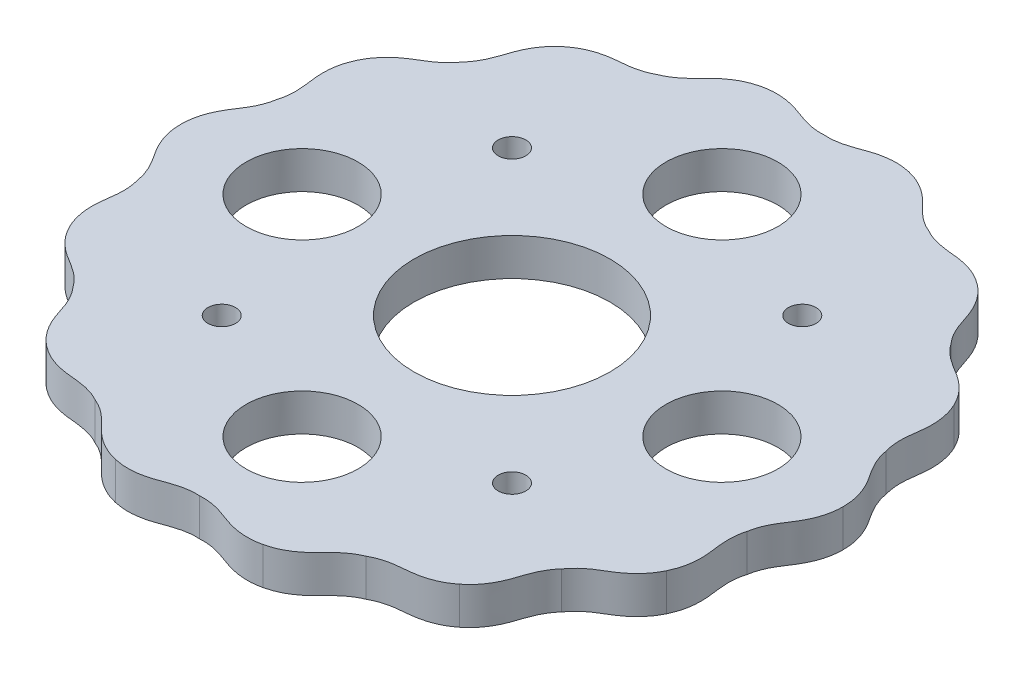
SolidWorks part; units mm, degrees
ref_plane "Front Plane" through (0, 0, 0) normal (0, 0, 1) x (1, 0, 0)
ref_plane "Top Plane" through (0, 0, 0) normal (0, 1, 0) x (1, 0, 0)
ref_plane "Right Plane" through (0, 0, 0) normal (1, 0, 0) x (0, 0, -1)
sketch "Sketch1" plane through (0, 0, 0) normal (0, 1, 0) x (1, 0, 0)
  line L0 (0, 0) -> (37.5, 0) construction
  line L1 (0, 0) -> (37.4807, 1.2019) construction
  line L2 (0, 0) -> (37.423, 2.4026) construction
  line L3 (0, 0) -> (37.3267, 3.6009) construction
  line L4 (0, 0) -> (37.1921, 4.7954) construction
  line L5 (0, 0) -> (37.0193, 5.985) construction
  line L6 (0, 0) -> (36.8085, 7.1684) construction
  line L7 (0, 0) -> (36.5598, 8.3445) construction
  line L8 (0, 0) -> (36.2736, 9.512) construction
  line L9 (0, 0) -> (35.95, 10.6698) construction
  line L10 (0, 0) -> (35.5896, 11.8166) construction
  line L11 (0, 0) -> (35.1926, 12.9512) construction
  line L12 (0, 0) -> (34.7594, 14.0725) construction
  line L13 (0, 0) -> (34.2905, 15.1794) construction
  line L14 (0, 0) -> (33.7863, 16.2706) construction
  line L15 (37.5, 0) -> (38.5, 0) construction
  line L16 (37.4807, 1.2019) -> (38.3521, 1.6927) construction
  line L17 (37.423, 2.4026) -> (37.9413, 3.2578) construction
  line L18 (37.3267, 3.6009) -> (37.3588, 4.6003) construction
  line L19 (37.1921, 4.7954) -> (36.7296, 5.682) construction
  line L20 (37.0193, 5.985) -> (36.1812, 6.5305) construction
  line L21 (36.8085, 7.1684) -> (35.8105, 7.2325) construction
  line L22 (36.5598, 8.3445) -> (35.5849, 8.122) construction
  line L23 (37, 0.0019) -> (37, 0)
  line L24 (33.3367, 16.052) -> (33.3358, 16.0537)
  line L25 (37, -0.0019) -> (37, 0)
  line L26 (33.3367, -16.052) -> (33.3358, -16.0537)
  line L27 (33.335, -16.0554) -> (33.3358, -16.0537)
  line L28 (23.0706, -28.9266) -> (23.0691, -28.9278)
  line L29 (23.0677, -28.9289) -> (23.0691, -28.9278)
  line L30 (8.2351, -36.0719) -> (8.2333, -36.0723)
  line L31 (8.2315, -36.0727) -> (8.2333, -36.0723)
  line L32 (-8.2315, -36.0727) -> (-8.2333, -36.0723)
  line L33 (-8.2351, -36.0719) -> (-8.2333, -36.0723)
  line L34 (-23.0677, -28.9289) -> (-23.0691, -28.9278)
  line L35 (-23.0706, -28.9266) -> (-23.0691, -28.9278)
  line L36 (-33.335, -16.0554) -> (-33.3358, -16.0537)
  line L37 (-33.3367, -16.052) -> (-33.3358, -16.0537)
  line L38 (-37, -0.0019) -> (-37, 0)
  line L39 (-37, 0.0019) -> (-37, 0)
  line L40 (-33.3367, 16.052) -> (-33.3358, 16.0537)
  line L41 (-33.335, 16.0554) -> (-33.3358, 16.0537)
  line L42 (-23.0706, 28.9266) -> (-23.0691, 28.9278)
  line L43 (-23.0677, 28.9289) -> (-23.0691, 28.9278)
  line L44 (-8.2351, 36.0719) -> (-8.2333, 36.0723)
  line L45 (-8.2315, 36.0727) -> (-8.2333, 36.0723)
  line L46 (8.2315, 36.0727) -> (8.2333, 36.0723)
  line L47 (8.2351, 36.0719) -> (8.2333, 36.0723)
  line L48 (23.0677, 28.9289) -> (23.0691, 28.9278)
  line L49 (23.0706, 28.9266) -> (23.0691, 28.9278)
  line L50 (33.335, 16.0554) -> (33.3358, 16.0537)
  line L51 (35.5, 0.0037) -> (35.5, 0)
  line L52 (31.986, 15.3995) -> (31.9844, 15.4029)
  line L53 (35.5, -0.0037) -> (35.5, 0)
  line L54 (31.986, -15.3995) -> (31.9844, -15.4029)
  line L55 (31.9828, -15.4062) -> (31.9844, -15.4029)
  line L56 (22.1368, -27.7527) -> (22.1339, -27.755)
  line L57 (22.131, -27.7573) -> (22.1339, -27.755)
  line L58 (7.9031, -34.6091) -> (7.8995, -34.6099)
  line L59 (7.8959, -34.6108) -> (7.8995, -34.6099)
  line L60 (-7.8959, -34.6108) -> (-7.8995, -34.6099)
  line L61 (-7.9031, -34.6091) -> (-7.8995, -34.6099)
  line L62 (-22.131, -27.7573) -> (-22.1339, -27.755)
  line L63 (-22.1368, -27.7527) -> (-22.1339, -27.755)
  line L64 (-31.9828, -15.4062) -> (-31.9844, -15.4029)
  line L65 (-31.986, -15.3995) -> (-31.9844, -15.4029)
  line L66 (-35.5, -0.0037) -> (-35.5, 0)
  line L67 (-35.5, 0.0037) -> (-35.5, 0)
  line L68 (-31.986, 15.3995) -> (-31.9844, 15.4029)
  line L69 (-31.9828, 15.4062) -> (-31.9844, 15.4029)
  line L70 (-22.1368, 27.7527) -> (-22.1339, 27.755)
  line L71 (-22.131, 27.7573) -> (-22.1339, 27.755)
  line L72 (-7.9031, 34.6091) -> (-7.8995, 34.6099)
  line L73 (-7.8959, 34.6108) -> (-7.8995, 34.6099)
  line L74 (7.8959, 34.6108) -> (7.8995, 34.6099)
  line L75 (7.9031, 34.6091) -> (7.8995, 34.6099)
  line L76 (22.131, 27.7573) -> (22.1339, 27.755)
  line L77 (22.1368, 27.7527) -> (22.1339, 27.755)
  line L78 (31.9828, 15.4062) -> (31.9844, 15.4029)
  circle A0 centre (0, 0) radius 35 construction
  circle A1 centre (37.5, 0) radius 2.5 construction
  circle A2 centre (0, 0) radius 37.5 construction
  spline S0 degree 3 poles (35.5849, 8.122) (35.6266, 7.5364) (36.0345, 6.7125) (36.7836, 5.6218) (37.4152, 4.5501) (38.2239, 2.702) (38.5014, 1.1074) (38.5, 0) knots 0 0 0 0 0.195516 0.310928 0.453873 0.621058 1 1 1 1
  spline S1 degree 3 poles (35.5849, 8.122) (35.3683, 8.6678) (35.3784, 9.5871) (35.5801, 10.8948) (35.6841, 12.1344) (35.611, 14.1503) (35.169, 15.7074) (34.6873, 16.7045) knots 0 0 0 0 0.195516 0.310928 0.453873 0.621058 1 1 1 1
  spline S2 degree 1 poles (34.1119, 7.7858) (33.3367, 16.052) knots 0 0 1 1 construction
  spline S3 degree 1 poles (34.1119, 7.7858) (37, 0.0019) knots 0 0 1 1 construction
  spline S4 degree 3 poles (33.3367, 16.052) (33.6005, 15.5058) (33.9037, 14.6401) (34.1146, 13.4372) (34.174, 12.5211) (34.1413, 11.5771) (34.0239, 10.6392) (33.8823, 9.6155) (33.9055, 8.625) (34.0243, 8.0514) (34.1119, 7.7858) knots 0.015853 0.015853 0.015853 0.015853 0.26189 0.384908 0.507927 0.630945 0.753963 0.876982 0.938491 1 1 1 1
  spline S5 degree 3 poles (34.1119, 7.7858) (34.1483, 7.5085) (34.2901, 6.9402) (34.6989, 6.0377) (35.2706, 5.1769) (35.7834, 4.3828) (36.2224, 3.5464) (36.5664, 2.6953) (36.8983, 1.52) (37.0008, 0.6085) (37, 0.0019) knots 0.015853 0.015853 0.015853 0.015853 0.077362 0.138872 0.26189 0.384908 0.507927 0.630945 0.753963 1 1 1 1
  spline S6 degree 3 poles (37, -0.0019) (37.0008, -0.6085) (36.8983, -1.52) (36.5664, -2.6953) (36.2224, -3.5464) (35.7834, -4.3828) (35.2706, -5.1769) (34.6989, -6.0377) (34.2901, -6.9402) (34.1483, -7.5085) (34.1119, -7.7858) knots 0.015853 0.015853 0.015853 0.015853 0.26189 0.384908 0.507927 0.630945 0.753963 0.876982 0.938491 1 1 1 1
  spline S7 degree 3 poles (34.1119, -7.7858) (34.0243, -8.0514) (33.9055, -8.625) (33.8823, -9.6155) (34.0239, -10.6392) (34.1413, -11.5771) (34.174, -12.5211) (34.1146, -13.4372) (33.9037, -14.6401) (33.6005, -15.5058) (33.3367, -16.052) knots 0.015853 0.015853 0.015853 0.015853 0.077362 0.138872 0.26189 0.384908 0.507927 0.630945 0.753963 1 1 1 1
  spline S8 degree 3 poles (33.335, -16.0554) (33.0725, -16.6022) (32.5847, -17.3791) (31.7758, -18.2939) (31.0965, -18.9115) (30.3381, -19.4746) (29.5316, -19.9675) (28.6429, -20.4951) (27.8831, -21.1308) (27.5087, -21.5813) (27.3556, -21.8154) knots 0.015853 0.015853 0.015853 0.015853 0.26189 0.384908 0.507927 0.630945 0.753963 0.876982 0.938491 1 1 1 1
  spline S9 degree 3 poles (27.3556, -21.8154) (27.1615, -22.0167) (26.8056, -22.4819) (26.3549, -23.3642) (26.0383, -24.348) (25.7371, -25.2439) (25.357, -26.1087) (24.906, -26.9083) (24.1941, -27.9005) (23.5453, -28.549) (23.0706, -28.9266) knots 0.015853 0.015853 0.015853 0.015853 0.077362 0.138872 0.26189 0.384908 0.507927 0.630945 0.753963 1 1 1 1
  spline S10 degree 3 poles (23.0677, -28.9289) (22.5939, -29.3077) (21.8173, -29.796) (20.6915, -30.2693) (19.8116, -30.531) (18.884, -30.7092) (17.9435, -30.8034) (16.9139, -30.8931) (15.9535, -31.1362) (15.4207, -31.3797) (15.1812, -31.5241) knots 0.015853 0.015853 0.015853 0.015853 0.26189 0.384908 0.507927 0.630945 0.753963 0.876982 0.938491 1 1 1 1
  spline S11 degree 3 poles (15.1812, -31.5241) (14.919, -31.6213) (14.3964, -31.886) (13.6076, -32.4854) (12.8955, -33.2344) (12.2354, -33.9109) (11.5177, -34.5251) (10.7645, -35.0499) (9.6926, -35.6349) (8.8266, -35.9377) (8.2351, -36.0719) knots 0.015853 0.015853 0.015853 0.015853 0.077362 0.138872 0.26189 0.384908 0.507927 0.630945 0.753963 1 1 1 1
  spline S12 degree 3 poles (8.2315, -36.0727) (7.6402, -36.2085) (6.7287, -36.3114) (5.5091, -36.2494) (4.6028, -36.1034) (3.6897, -35.8614) (2.8014, -35.5383) (1.8349, -35.1724) (0.8641, -34.9747) (0.2785, -34.9629) (0, -34.9891) knots 0.015853 0.015853 0.015853 0.015853 0.26189 0.384908 0.507927 0.630945 0.753963 0.876982 0.938491 1 1 1 1
  spline S13 degree 3 poles (0, -34.9891) (-0.2785, -34.9629) (-0.8641, -34.9747) (-1.8349, -35.1724) (-2.8014, -35.5383) (-3.6897, -35.8614) (-4.6028, -36.1034) (-5.5091, -36.2494) (-6.7287, -36.3114) (-7.6402, -36.2085) (-8.2315, -36.0727) knots 0.015853 0.015853 0.015853 0.015853 0.077362 0.138872 0.26189 0.384908 0.507927 0.630945 0.753963 1 1 1 1
  spline S14 degree 3 poles (-8.2351, -36.0719) (-8.8266, -35.9377) (-9.6926, -35.6349) (-10.7645, -35.0499) (-11.5177, -34.5251) (-12.2354, -33.9109) (-12.8955, -33.2344) (-13.6076, -32.4854) (-14.3964, -31.886) (-14.919, -31.6213) (-15.1812, -31.5241) knots 0.015853 0.015853 0.015853 0.015853 0.26189 0.384908 0.507927 0.630945 0.753963 0.876982 0.938491 1 1 1 1
  spline S15 degree 3 poles (-15.1812, -31.5241) (-15.4207, -31.3797) (-15.9535, -31.1362) (-16.9139, -30.8931) (-17.9435, -30.8034) (-18.884, -30.7092) (-19.8116, -30.531) (-20.6915, -30.2693) (-21.8173, -29.796) (-22.5939, -29.3077) (-23.0677, -28.9289) knots 0.015853 0.015853 0.015853 0.015853 0.077362 0.138872 0.26189 0.384908 0.507927 0.630945 0.753963 1 1 1 1
  spline S16 degree 3 poles (-23.0706, -28.9266) (-23.5453, -28.549) (-24.1941, -27.9005) (-24.906, -26.9083) (-25.357, -26.1087) (-25.7371, -25.2439) (-26.0383, -24.348) (-26.3549, -23.3642) (-26.8056, -22.4819) (-27.1615, -22.0167) (-27.3556, -21.8154) knots 0.015853 0.015853 0.015853 0.015853 0.26189 0.384908 0.507927 0.630945 0.753963 0.876982 0.938491 1 1 1 1
  spline S17 degree 3 poles (-27.3556, -21.8154) (-27.5087, -21.5813) (-27.8831, -21.1308) (-28.6429, -20.4951) (-29.5316, -19.9675) (-30.3381, -19.4746) (-31.0965, -18.9115) (-31.7758, -18.2939) (-32.5847, -17.3791) (-33.0725, -16.6022) (-33.335, -16.0554) knots 0.015853 0.015853 0.015853 0.015853 0.077362 0.138872 0.26189 0.384908 0.507927 0.630945 0.753963 1 1 1 1
  spline S18 degree 3 poles (-33.3367, -16.052) (-33.6005, -15.5058) (-33.9037, -14.6401) (-34.1146, -13.4372) (-34.174, -12.5211) (-34.1413, -11.5771) (-34.0239, -10.6392) (-33.8823, -9.6155) (-33.9055, -8.625) (-34.0243, -8.0514) (-34.1119, -7.7858) knots 0.015853 0.015853 0.015853 0.015853 0.26189 0.384908 0.507927 0.630945 0.753963 0.876982 0.938491 1 1 1 1
  spline S19 degree 3 poles (-34.1119, -7.7858) (-34.1483, -7.5085) (-34.2901, -6.9402) (-34.6989, -6.0377) (-35.2706, -5.1769) (-35.7834, -4.3828) (-36.2224, -3.5464) (-36.5664, -2.6953) (-36.8983, -1.52) (-37.0008, -0.6085) (-37, -0.0019) knots 0.015853 0.015853 0.015853 0.015853 0.077362 0.138872 0.26189 0.384908 0.507927 0.630945 0.753963 1 1 1 1
  spline S20 degree 3 poles (-37, 0.0019) (-37.0008, 0.6085) (-36.8983, 1.52) (-36.5664, 2.6953) (-36.2224, 3.5464) (-35.7834, 4.3828) (-35.2706, 5.1769) (-34.6989, 6.0377) (-34.2901, 6.9402) (-34.1483, 7.5085) (-34.1119, 7.7858) knots 0.015853 0.015853 0.015853 0.015853 0.26189 0.384908 0.507927 0.630945 0.753963 0.876982 0.938491 1 1 1 1
  spline S21 degree 3 poles (-34.1119, 7.7858) (-34.0243, 8.0514) (-33.9055, 8.625) (-33.8823, 9.6155) (-34.0239, 10.6392) (-34.1413, 11.5771) (-34.174, 12.5211) (-34.1146, 13.4372) (-33.9037, 14.6401) (-33.6005, 15.5058) (-33.3367, 16.052) knots 0.015853 0.015853 0.015853 0.015853 0.077362 0.138872 0.26189 0.384908 0.507927 0.630945 0.753963 1 1 1 1
  spline S22 degree 3 poles (-33.335, 16.0554) (-33.0725, 16.6022) (-32.5847, 17.3791) (-31.7758, 18.2939) (-31.0965, 18.9115) (-30.3381, 19.4746) (-29.5316, 19.9675) (-28.6429, 20.4951) (-27.8831, 21.1308) (-27.5087, 21.5813) (-27.3556, 21.8154) knots 0.015853 0.015853 0.015853 0.015853 0.26189 0.384908 0.507927 0.630945 0.753963 0.876982 0.938491 1 1 1 1
  spline S23 degree 3 poles (-27.3556, 21.8154) (-27.1615, 22.0167) (-26.8056, 22.4819) (-26.3549, 23.3642) (-26.0383, 24.348) (-25.7371, 25.2439) (-25.357, 26.1087) (-24.906, 26.9083) (-24.1941, 27.9005) (-23.5453, 28.549) (-23.0706, 28.9266) knots 0.015853 0.015853 0.015853 0.015853 0.077362 0.138872 0.26189 0.384908 0.507927 0.630945 0.753963 1 1 1 1
  spline S24 degree 3 poles (-23.0677, 28.9289) (-22.5939, 29.3077) (-21.8173, 29.796) (-20.6915, 30.2693) (-19.8116, 30.531) (-18.884, 30.7092) (-17.9435, 30.8034) (-16.9139, 30.8931) (-15.9535, 31.1362) (-15.4207, 31.3797) (-15.1812, 31.5241) knots 0.015853 0.015853 0.015853 0.015853 0.26189 0.384908 0.507927 0.630945 0.753963 0.876982 0.938491 1 1 1 1
  spline S25 degree 3 poles (-15.1812, 31.5241) (-14.919, 31.6213) (-14.3964, 31.886) (-13.6076, 32.4854) (-12.8955, 33.2344) (-12.2354, 33.9109) (-11.5177, 34.5251) (-10.7645, 35.0499) (-9.6926, 35.6349) (-8.8266, 35.9377) (-8.2351, 36.0719) knots 0.015853 0.015853 0.015853 0.015853 0.077362 0.138872 0.26189 0.384908 0.507927 0.630945 0.753963 1 1 1 1
  spline S26 degree 3 poles (-8.2315, 36.0727) (-7.6402, 36.2085) (-6.7287, 36.3114) (-5.5091, 36.2494) (-4.6028, 36.1034) (-3.6897, 35.8614) (-2.8014, 35.5383) (-1.8349, 35.1724) (-0.8641, 34.9747) (-0.2785, 34.9629) (0, 34.9891) knots 0.015853 0.015853 0.015853 0.015853 0.26189 0.384908 0.507927 0.630945 0.753963 0.876982 0.938491 1 1 1 1
  spline S27 degree 3 poles (0, 34.9891) (0.2785, 34.9629) (0.8641, 34.9747) (1.8349, 35.1724) (2.8014, 35.5383) (3.6897, 35.8614) (4.6028, 36.1034) (5.5091, 36.2494) (6.7287, 36.3114) (7.6402, 36.2085) (8.2315, 36.0727) knots 0.015853 0.015853 0.015853 0.015853 0.077362 0.138872 0.26189 0.384908 0.507927 0.630945 0.753963 1 1 1 1
  spline S28 degree 3 poles (8.2351, 36.0719) (8.8266, 35.9377) (9.6926, 35.6349) (10.7645, 35.0499) (11.5177, 34.5251) (12.2354, 33.9109) (12.8955, 33.2344) (13.6076, 32.4854) (14.3964, 31.886) (14.919, 31.6213) (15.1812, 31.5241) knots 0.015853 0.015853 0.015853 0.015853 0.26189 0.384908 0.507927 0.630945 0.753963 0.876982 0.938491 1 1 1 1
  spline S29 degree 3 poles (15.1812, 31.5241) (15.4207, 31.3797) (15.9535, 31.1362) (16.9139, 30.8931) (17.9435, 30.8034) (18.884, 30.7092) (19.8116, 30.531) (20.6915, 30.2693) (21.8173, 29.796) (22.5939, 29.3077) (23.0677, 28.9289) knots 0.015853 0.015853 0.015853 0.015853 0.077362 0.138872 0.26189 0.384908 0.507927 0.630945 0.753963 1 1 1 1
  spline S30 degree 3 poles (23.0706, 28.9266) (23.5453, 28.549) (24.1941, 27.9005) (24.906, 26.9083) (25.357, 26.1087) (25.7371, 25.2439) (26.0383, 24.348) (26.3549, 23.3642) (26.8056, 22.4819) (27.1615, 22.0167) (27.3556, 21.8154) knots 0.015853 0.015853 0.015853 0.015853 0.26189 0.384908 0.507927 0.630945 0.753963 0.876982 0.938491 1 1 1 1
  spline S31 degree 3 poles (27.3556, 21.8154) (27.5087, 21.5813) (27.8831, 21.1308) (28.6429, 20.4951) (29.5316, 19.9675) (30.3381, 19.4746) (31.0965, 18.9115) (31.7758, 18.2939) (32.5847, 17.3791) (33.0725, 16.6022) (33.335, 16.0554) knots 0.015853 0.015853 0.015853 0.015853 0.077362 0.138872 0.26189 0.384908 0.507927 0.630945 0.753963 1 1 1 1
  spline S32 degree 1 poles (32.6448, 7.451) (35.5, 0.0037) knots 0 0 1 1 construction
  spline S33 degree 1 poles (32.6448, 7.451) (31.986, 15.3995) knots 0 0 1 1 construction
  spline S34 degree 3 poles (35.5, 0.0037) (35.5006, 0.4959) (35.4183, 1.2336) (35.1496, 2.1927) (34.8707, 2.8896) (34.4997, 3.6015) (34.1394, 4.1652) (33.6939, 4.8394) (33.3068, 5.4873) (32.9751, 6.1975) (32.758, 6.8733) (32.6748, 7.2607) (32.6448, 7.451) knots 0.023011 0.023011 0.023011 0.023011 0.267258 0.389382 0.511505 0.633629 0.755753 0.816814 0.877876 0.938938 0.969469 1 1 1 1
  spline S35 degree 3 poles (32.6448, 7.451) (32.5893, 7.6354) (32.4961, 8.0206) (32.3985, 8.7236) (32.3893, 9.5074) (32.4569, 10.2591) (32.5657, 11.0598) (32.6458, 11.724) (32.6712, 12.5264) (32.6201, 13.2752) (32.446, 14.256) (32.2001, 14.9563) (31.986, 15.3995) knots 0.023011 0.023011 0.023011 0.023011 0.053542 0.084072 0.145134 0.206196 0.267258 0.389382 0.511505 0.633629 0.755753 1 1 1 1
  spline S36 degree 3 poles (32.6448, -7.451) (32.6748, -7.2607) (32.758, -6.8733) (32.9751, -6.1975) (33.3068, -5.4873) (33.6939, -4.8394) (34.1394, -4.1652) (34.4997, -3.6015) (34.8707, -2.8896) (35.1496, -2.1927) (35.4183, -1.2336) (35.5006, -0.4959) (35.5, -0.0037) knots 0.023011 0.023011 0.023011 0.023011 0.053542 0.084072 0.145134 0.206196 0.267258 0.389382 0.511505 0.633629 0.755753 1 1 1 1
  spline S37 degree 3 poles (31.986, -15.3995) (32.2001, -14.9563) (32.446, -14.256) (32.6201, -13.2752) (32.6712, -12.5264) (32.6458, -11.724) (32.5657, -11.0598) (32.4569, -10.2591) (32.3893, -9.5074) (32.3985, -8.7236) (32.4961, -8.0206) (32.5893, -7.6354) (32.6448, -7.451) knots 0.023011 0.023011 0.023011 0.023011 0.267258 0.389382 0.511505 0.633629 0.755753 0.816814 0.877876 0.938938 0.969469 1 1 1 1
  spline S38 degree 3 poles (26.1791, -20.8771) (26.2887, -20.7187) (26.5317, -20.4057) (27.0205, -19.8911) (27.6275, -19.3952) (28.2574, -18.9793) (28.9513, -18.5652) (29.5206, -18.2137) (30.1637, -17.7333) (30.7173, -17.2264) (31.3755, -16.4789) (31.7698, -15.8499) (31.9828, -15.4062) knots 0.023011 0.023011 0.023011 0.023011 0.053542 0.084072 0.145134 0.206196 0.267258 0.389382 0.511505 0.633629 0.755753 1 1 1 1
  spline S39 degree 3 poles (22.1368, -27.7527) (22.522, -27.4463) (23.0474, -26.922) (23.6297, -26.1139) (24.0007, -25.4614) (24.326, -24.7275) (24.542, -24.0943) (24.7914, -23.3257) (25.0566, -22.619) (25.405, -21.9169) (25.798, -21.3258) (26.0491, -21.0192) (26.1791, -20.8771) knots 0.023011 0.023011 0.023011 0.023011 0.267258 0.389382 0.511505 0.633629 0.755753 0.816814 0.877876 0.938938 0.969469 1 1 1 1
  spline S40 degree 3 poles (14.5283, -30.1683) (14.6957, -30.0732) (15.0505, -29.8966) (15.7143, -29.645) (16.4763, -29.4616) (17.2242, -29.3602) (18.0291, -29.2882) (18.6945, -29.2185) (19.4823, -29.0647) (20.201, -28.8482) (21.1184, -28.4603) (21.7465, -28.0647) (22.131, -27.7573) knots 0.023011 0.023011 0.023011 0.023011 0.053542 0.084072 0.145134 0.206196 0.267258 0.389382 0.511505 0.633629 0.755753 1 1 1 1
  spline S41 degree 3 poles (7.9031, -34.6091) (8.3831, -34.5002) (9.084, -34.2557) (9.9593, -33.7804) (10.5766, -33.3534) (11.1881, -32.8334) (11.6575, -32.3566) (12.2156, -31.7723) (12.7612, -31.2507) (13.3797, -30.7693) (13.9903, -30.4072) (14.3495, -30.2399) (14.5283, -30.1683) knots 0.023011 0.023011 0.023011 0.023011 0.267258 0.389382 0.511505 0.633629 0.755753 0.816814 0.877876 0.938938 0.969469 1 1 1 1
  spline S42 degree 3 poles (0, -33.4843) (0.1922, -33.4712) (0.5884, -33.4661) (1.2956, -33.5274) (2.0617, -33.6928) (2.7796, -33.926) (3.536, -34.2103) (4.1657, -34.4362) (4.9423, -34.6394) (5.6838, -34.7562) (6.6786, -34.8048) (7.4161, -34.7209) (7.8959, -34.6108) knots 0.023011 0.023011 0.023011 0.023011 0.053542 0.084072 0.145134 0.206196 0.267258 0.389382 0.511505 0.633629 0.755753 1 1 1 1
  spline S43 degree 3 poles (-7.8959, -34.6108) (-7.4161, -34.7209) (-6.6786, -34.8048) (-5.6838, -34.7562) (-4.9423, -34.6394) (-4.1657, -34.4362) (-3.536, -34.2103) (-2.7796, -33.926) (-2.0617, -33.6928) (-1.2956, -33.5274) (-0.5884, -33.4661) (-0.1922, -33.4712) (0, -33.4843) knots 0.023011 0.023011 0.023011 0.023011 0.267258 0.389382 0.511505 0.633629 0.755753 0.816814 0.877876 0.938938 0.969469 1 1 1 1
  spline S44 degree 3 poles (-14.5283, -30.1683) (-14.3495, -30.2399) (-13.9903, -30.4072) (-13.3797, -30.7693) (-12.7612, -31.2507) (-12.2156, -31.7723) (-11.6575, -32.3566) (-11.1881, -32.8334) (-10.5766, -33.3534) (-9.9593, -33.7804) (-9.084, -34.2557) (-8.3831, -34.5002) (-7.9031, -34.6091) knots 0.023011 0.023011 0.023011 0.023011 0.053542 0.084072 0.145134 0.206196 0.267258 0.389382 0.511505 0.633629 0.755753 1 1 1 1
  spline S45 degree 3 poles (-22.131, -27.7573) (-21.7465, -28.0647) (-21.1184, -28.4603) (-20.201, -28.8482) (-19.4823, -29.0647) (-18.6945, -29.2185) (-18.0291, -29.2882) (-17.2242, -29.3602) (-16.4763, -29.4616) (-15.7143, -29.645) (-15.0505, -29.8966) (-14.6957, -30.0732) (-14.5283, -30.1683) knots 0.023011 0.023011 0.023011 0.023011 0.267258 0.389382 0.511505 0.633629 0.755753 0.816814 0.877876 0.938938 0.969469 1 1 1 1
  spline S46 degree 3 poles (-26.1791, -20.8771) (-26.0491, -21.0192) (-25.798, -21.3258) (-25.405, -21.9169) (-25.0566, -22.619) (-24.7914, -23.3257) (-24.542, -24.0943) (-24.326, -24.7275) (-24.0007, -25.4614) (-23.6297, -26.1139) (-23.0474, -26.922) (-22.522, -27.4463) (-22.1368, -27.7527) knots 0.023011 0.023011 0.023011 0.023011 0.053542 0.084072 0.145134 0.206196 0.267258 0.389382 0.511505 0.633629 0.755753 1 1 1 1
  spline S47 degree 3 poles (-31.9828, -15.4062) (-31.7698, -15.8499) (-31.3755, -16.4789) (-30.7173, -17.2264) (-30.1637, -17.7333) (-29.5206, -18.2137) (-28.9513, -18.5652) (-28.2574, -18.9793) (-27.6275, -19.3952) (-27.0205, -19.8911) (-26.5317, -20.4057) (-26.2887, -20.7187) (-26.1791, -20.8771) knots 0.023011 0.023011 0.023011 0.023011 0.267258 0.389382 0.511505 0.633629 0.755753 0.816814 0.877876 0.938938 0.969469 1 1 1 1
  spline S48 degree 3 poles (-32.6448, -7.451) (-32.5893, -7.6354) (-32.4961, -8.0206) (-32.3985, -8.7236) (-32.3893, -9.5074) (-32.4569, -10.2591) (-32.5657, -11.0598) (-32.6458, -11.724) (-32.6712, -12.5264) (-32.6201, -13.2752) (-32.446, -14.256) (-32.2001, -14.9563) (-31.986, -15.3995) knots 0.023011 0.023011 0.023011 0.023011 0.053542 0.084072 0.145134 0.206196 0.267258 0.389382 0.511505 0.633629 0.755753 1 1 1 1
  spline S49 degree 3 poles (-35.5, -0.0037) (-35.5006, -0.4959) (-35.4183, -1.2336) (-35.1496, -2.1927) (-34.8707, -2.8896) (-34.4997, -3.6015) (-34.1394, -4.1652) (-33.6939, -4.8394) (-33.3068, -5.4873) (-32.9751, -6.1975) (-32.758, -6.8733) (-32.6748, -7.2607) (-32.6448, -7.451) knots 0.023011 0.023011 0.023011 0.023011 0.267258 0.389382 0.511505 0.633629 0.755753 0.816814 0.877876 0.938938 0.969469 1 1 1 1
  spline S50 degree 3 poles (-32.6448, 7.451) (-32.6748, 7.2607) (-32.758, 6.8733) (-32.9751, 6.1975) (-33.3068, 5.4873) (-33.6939, 4.8394) (-34.1394, 4.1652) (-34.4997, 3.6015) (-34.8707, 2.8896) (-35.1496, 2.1927) (-35.4183, 1.2336) (-35.5006, 0.4959) (-35.5, 0.0037) knots 0.023011 0.023011 0.023011 0.023011 0.053542 0.084072 0.145134 0.206196 0.267258 0.389382 0.511505 0.633629 0.755753 1 1 1 1
  spline S51 degree 3 poles (-31.986, 15.3995) (-32.2001, 14.9563) (-32.446, 14.256) (-32.6201, 13.2752) (-32.6712, 12.5264) (-32.6458, 11.724) (-32.5657, 11.0598) (-32.4569, 10.2591) (-32.3893, 9.5074) (-32.3985, 8.7236) (-32.4961, 8.0206) (-32.5893, 7.6354) (-32.6448, 7.451) knots 0.023011 0.023011 0.023011 0.023011 0.267258 0.389382 0.511505 0.633629 0.755753 0.816814 0.877876 0.938938 0.969469 1 1 1 1
  spline S52 degree 3 poles (-26.1791, 20.8771) (-26.2887, 20.7187) (-26.5317, 20.4057) (-27.0205, 19.8911) (-27.6275, 19.3952) (-28.2574, 18.9793) (-28.9513, 18.5652) (-29.5206, 18.2137) (-30.1637, 17.7333) (-30.7173, 17.2264) (-31.3755, 16.4789) (-31.7698, 15.8499) (-31.9828, 15.4062) knots 0.023011 0.023011 0.023011 0.023011 0.053542 0.084072 0.145134 0.206196 0.267258 0.389382 0.511505 0.633629 0.755753 1 1 1 1
  spline S53 degree 3 poles (-22.1368, 27.7527) (-22.522, 27.4463) (-23.0474, 26.922) (-23.6297, 26.1139) (-24.0007, 25.4614) (-24.326, 24.7275) (-24.542, 24.0943) (-24.7914, 23.3257) (-25.0566, 22.619) (-25.405, 21.9169) (-25.798, 21.3258) (-26.0491, 21.0192) (-26.1791, 20.8771) knots 0.023011 0.023011 0.023011 0.023011 0.267258 0.389382 0.511505 0.633629 0.755753 0.816814 0.877876 0.938938 0.969469 1 1 1 1
  spline S54 degree 3 poles (-14.5283, 30.1683) (-14.6957, 30.0732) (-15.0505, 29.8966) (-15.7143, 29.645) (-16.4763, 29.4616) (-17.2242, 29.3602) (-18.0291, 29.2882) (-18.6945, 29.2185) (-19.4823, 29.0647) (-20.201, 28.8482) (-21.1184, 28.4603) (-21.7465, 28.0647) (-22.131, 27.7573) knots 0.023011 0.023011 0.023011 0.023011 0.053542 0.084072 0.145134 0.206196 0.267258 0.389382 0.511505 0.633629 0.755753 1 1 1 1
  spline S55 degree 3 poles (-7.9031, 34.6091) (-8.3831, 34.5002) (-9.084, 34.2557) (-9.9593, 33.7804) (-10.5766, 33.3534) (-11.1881, 32.8334) (-11.6575, 32.3566) (-12.2156, 31.7723) (-12.7612, 31.2507) (-13.3797, 30.7693) (-13.9903, 30.4072) (-14.3495, 30.2399) (-14.5283, 30.1683) knots 0.023011 0.023011 0.023011 0.023011 0.267258 0.389382 0.511505 0.633629 0.755753 0.816814 0.877876 0.938938 0.969469 1 1 1 1
  spline S56 degree 3 poles (0, 33.4843) (-0.1922, 33.4712) (-0.5884, 33.4661) (-1.2956, 33.5274) (-2.0617, 33.6928) (-2.7796, 33.926) (-3.536, 34.2103) (-4.1657, 34.4362) (-4.9423, 34.6394) (-5.6838, 34.7562) (-6.6786, 34.8048) (-7.4161, 34.7209) (-7.8959, 34.6108) knots 0.023011 0.023011 0.023011 0.023011 0.053542 0.084072 0.145134 0.206196 0.267258 0.389382 0.511505 0.633629 0.755753 1 1 1 1
  spline S57 degree 3 poles (7.8959, 34.6108) (7.4161, 34.7209) (6.6786, 34.8048) (5.6838, 34.7562) (4.9423, 34.6394) (4.1657, 34.4362) (3.536, 34.2103) (2.7796, 33.926) (2.0617, 33.6928) (1.2956, 33.5274) (0.5884, 33.4661) (0.1922, 33.4712) (0, 33.4843) knots 0.023011 0.023011 0.023011 0.023011 0.267258 0.389382 0.511505 0.633629 0.755753 0.816814 0.877876 0.938938 0.969469 1 1 1 1
  spline S58 degree 3 poles (14.5283, 30.1683) (14.3495, 30.2399) (13.9903, 30.4072) (13.3797, 30.7693) (12.7612, 31.2507) (12.2156, 31.7723) (11.6575, 32.3566) (11.1881, 32.8334) (10.5766, 33.3534) (9.9593, 33.7804) (9.084, 34.2557) (8.3831, 34.5002) (7.9031, 34.6091) knots 0.023011 0.023011 0.023011 0.023011 0.053542 0.084072 0.145134 0.206196 0.267258 0.389382 0.511505 0.633629 0.755753 1 1 1 1
  spline S59 degree 3 poles (22.131, 27.7573) (21.7465, 28.0647) (21.1184, 28.4603) (20.201, 28.8482) (19.4823, 29.0647) (18.6945, 29.2185) (18.0291, 29.2882) (17.2242, 29.3602) (16.4763, 29.4616) (15.7143, 29.645) (15.0505, 29.8966) (14.6957, 30.0732) (14.5283, 30.1683) knots 0.023011 0.023011 0.023011 0.023011 0.267258 0.389382 0.511505 0.633629 0.755753 0.816814 0.877876 0.938938 0.969469 1 1 1 1
  spline S60 degree 3 poles (26.1791, 20.8771) (26.0491, 21.0192) (25.798, 21.3258) (25.405, 21.9169) (25.0566, 22.619) (24.7914, 23.3257) (24.542, 24.0943) (24.326, 24.7275) (24.0007, 25.4614) (23.6297, 26.1139) (23.0474, 26.922) (22.522, 27.4463) (22.1368, 27.7527) knots 0.023011 0.023011 0.023011 0.023011 0.053542 0.084072 0.145134 0.206196 0.267258 0.389382 0.511505 0.633629 0.755753 1 1 1 1
  spline S61 degree 3 poles (31.9828, 15.4062) (31.7698, 15.8499) (31.3755, 16.4789) (30.7173, 17.2264) (30.1637, 17.7333) (29.5206, 18.2137) (28.9513, 18.5652) (28.2574, 18.9793) (27.6275, 19.3952) (27.0205, 19.8911) (26.5317, 20.4057) (26.2887, 20.7187) (26.1791, 20.8771) knots 0.023011 0.023011 0.023011 0.023011 0.267258 0.389382 0.511505 0.633629 0.755753 0.816814 0.877876 0.938938 0.969469 1 1 1 1
  point P25 (0, 0)
  point P117 (0, 0)
  point P174 (0, 0)
  dimension "D1" = 70
  dimension "D2" = 5
  dimension "D4" = 25.714
  dimension "D5" = 1
  dimension "D7" = 180
  dimension "D8" = 207.551
  dimension "D6" = 1
  dimension "D9" = 1
  dimension "D10" = 235.102
  dimension "D11" = 1
  dimension "D12" = 1
  dimension "D13" = 1
  dimension "D14" = 1
  dimension "D15" = 1
  dimension "D16" = 262.653
  dimension "D17" = 290.204
  dimension "D18" = 317.755
  dimension "D19" = 345.306
  dimension "D20" = 1.5
  dimension "D22" = 3
  dimension "D3" = 15
  dimension "D21" = 14
  dimension "D23" = 14
extrude "Boss-Extrude3" add sketch "Sketch1" along normal blind 4 contours L51 L53 S36 S37 L54 L55 S38 S39 L56 L57 S40 S41 L58 L59 S42 S43 L60 L61 S44 S45 L62 L63 S46 S47 L64 L65 S48 S49 L66 L67 S50 S51 L68 L69 S52 S53 L70 L71 S54 S55 L72 L73 S56 S57 L74 L75 S58 S59 L76 L77 S60 S61 L78 L52 S35 S34
sketch "Sketch2" plane through (0, 4, 0) normal (0, 1, 0) x (1, 0, 0)
  line L0 (0, 0) -> (22.5, 0) construction
  line L1 (0, 0) -> (15.5563, 15.5563) construction
  circle A0 centre (0, 0) radius 10.5
  circle A1 centre (22.5, 0) radius 6
  circle A6 centre (15.5563, 15.5563) radius 1.48
  circle A7 centre (0, -22.5) radius 6
  circle A8 centre (15.5563, -15.5563) radius 1.48
  circle A9 centre (-22.5, 0) radius 6
  circle A10 centre (-15.5563, -15.5563) radius 1.48
  circle A11 centre (0, 22.5) radius 6
  circle A12 centre (-15.5563, 15.5563) radius 1.48
  point P16 (0, 0)
  point P21 (0, 0)
  point P24 (0, 0)
  dimension "D3" = 12
  dimension "D1" = 21
  dimension "D6" = 2.96
  dimension "D2" = 22.5
  dimension "D4" = 45
  dimension "D5" = 22
  dimension "D7" = 4
extrude "Cut-Extrude1" cut sketch "Sketch2" against normal blind 5 contours A7 | A0 | A0 | A0 | L0 A0 | A0 L0 | A1 | A9 | A11 region at (0, 4, 0) region at (22.5, 4, 0) region at (0, 4, 22.5) region at (-22.5, 4, 0) region at (0, 4, -22.5)
extrude "Cut-Extrude2" cut sketch "Sketch2<4>" against normal blind 2.22 contours A12 | A10 | A8 | A6 region at (15.5563, 4, -15.5563) region at (15.5563, 4, 15.5563) region at (-15.5563, 4, 15.5563) region at (-15.5563, 4, -15.5563)
sketch "Sketch2<4>" plane through (0, 4, 0) normal (0, 1, 0) x (1, 0, 0) same geometry as "Sketch2"
equation "\"eccentricity\"= 1mm"
equation "\"Pin Diameter\"= 3mm"
equation "\"D5@Sketch1\" = \"eccentricity\""
equation "\"D6@Sketch1\" = \"eccentricity\""
equation "\"D9@Sketch1\" = \"eccentricity\""
equation "\"D11@Sketch1\" = \"eccentricity\""
equation "\"D12@Sketch1\" = \"eccentricity\""
equation "\"D14@Sketch1\" = \"eccentricity\""
equation "\"D13@Sketch1\" = \"eccentricity\""
equation "\"D15@Sketch1\" = \"eccentricity\""
equation "\"Disc Bearing Diameter\"=21"
equation "\"bearing_21_OD\"= 21mm"
equation "\"bearing_21_ID\"=15mm"
equation "\"pin_cirlce_diameter\"= 75mm"
equation "\"pin_diam\"= 6mm"
equation "\"gear_thickness\"= 4mm"
equation "\"ball_bearing_diam\"= 2.96mm"
equation "\"bearing_21_outer_clearance\"= 0mm'change this"
equation "\"bearing_21_inner_clearance\"=0mm'change this"
equation "\"bearing_15_OD\"= 15mm"
equation "\"bearing_15_ID\"=10mm"
equation "\"bearing_15_outer_clearance\"= 0mm'change this"
equation "\"bearing_15_inner_clearance\"= 0mm'change this"
equation "\"thrust_bearing_thickness\"= 5mm'measure this irl and change"
equation "\"D1@Sketch2\"=\"bearing_21_OD\"+\"bearing_21_outer_clearance\""
equation "\"D6@Sketch2\"=\"ball_bearing_diam\""
equation "\"D1@Cut-Extrude2\"=\"ball_bearing_diam\"*0.75"
